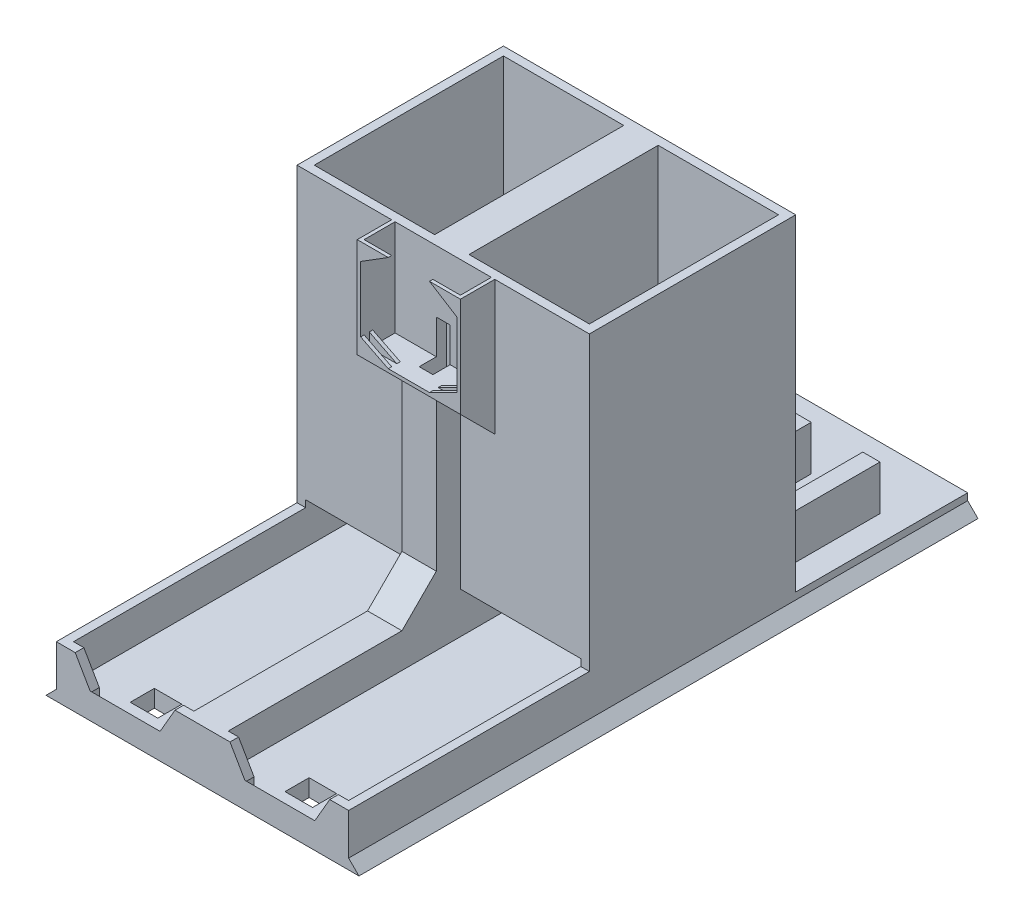
SolidWorks part; units mm, degrees
ref_plane "Front Plane" through (0, 0, 0) normal (0, 0, 1) x (1, 0, 0)
ref_plane "Top Plane" through (0, 0, 0) normal (0, 1, 0) x (1, 0, 0)
ref_plane "Right Plane" through (0, 0, 0) normal (1, 0, 0) x (0, 0, -1)
sketch "Sketch1" plane through (0, 0, 0) normal (0, 1, 0) x (1, 0, 0)
  line L1 (0, 0) -> (85, 0)
  line L2 (0, 0) -> (0, 60)
  line L3 (0, 60) -> (85, 60)
  line L4 (85, 0) -> (85, 60)
  dimension "D1" = 85
  dimension "D2" = 60
sketch "Sketch2" plane through (0, 0, 0) normal (0, 1, 0) x (1, 0, 0)
  line L1 (2.5, 57.5) -> (37.5, 57.5)
  line L2 (2.5, 57.5) -> (2.5, 2.5)
  line L3 (2.5, 2.5) -> (37.5, 2.5)
  line L4 (37.5, 57.5) -> (37.5, 2.5)
  line L5 (47.5, 57.5) -> (82.5, 57.5)
  line L6 (47.5, 57.5) -> (47.5, 2.5)
  line L7 (47.5, 2.5) -> (82.5, 2.5)
  line L8 (82.5, 57.5) -> (82.5, 2.5)
  dimension "D1" = 35
  dimension "D2" = 10
extrude "Boss-Extrude1" add sketch "Sketch1" along normal blind 100
extrude "Cut-Extrude1" cut sketch "Sketch2" along normal blind 95 from offset 5
sketch "Sketch3" plane through (0, 0, 0) normal (0, 0, 1) x (1, 0, 0)
  line L0 (85, 100) -> (85, 0) construction
  line L1 (0, 0) -> (85, 0)
  line L2 (0, 0) -> (0, 5)
  line L3 (0, 5) -> (85, 5)
  line L4 (85, 0) -> (85, 5)
extrude "Boss-Extrude2" add sketch "Sketch3" along normal blind 70
sketch "Sketch4" plane through (0, 5, 0) normal (0, 1, 0) x (1, 0, 0)
  line L0 (85, 0) -> (82.5, 0)
  line L5 (0, 0) -> (0, -70)
  line L18 (0, -70) -> (85, -70)
  line L19 (85, -70) -> (85, 0)
  line L20 (85, 0) -> (0, 0) construction
  line L21 (82.5, 0) -> (82.5, -67.5)
  line L22 (82.5, -67.5) -> (47.5, -67.5)
  line L23 (47.5, -67.5) -> (47.5, 0)
  line L24 (0, 0) -> (85, 0) construction
  line L25 (47.5, 0) -> (37.5, 0)
  line L26 (37.5, 0) -> (37.5, -67.5)
  line L27 (37.5, -67.5) -> (2.5, -67.5)
  line L28 (2.5, -67.5) -> (2.5, 0)
  line L29 (2.5, 0) -> (0, 0)
  dimension "D1" = 2.5
  dimension "D2" = 2.5
  dimension "D3" = 10
extrude "Boss-Extrude3" add sketch "Sketch4" along normal blind 10
sketch "Sketch5" plane through (0, 15, 0) normal (0, 1, 0) x (1, 0, 0)
  line L0 (37.5, -67.5) -> (2.5, -67.5) construction
  line L1 (10, -67.5) -> (30, -67.5)
  line L2 (10, -67.5) -> (10, -70)
  line L3 (10, -70) -> (30, -70)
  line L4 (30, -67.5) -> (30, -70)
  line L5 (0, -70) -> (85, -70) construction
  line L6 (82.5, -67.5) -> (47.5, -67.5) construction
  line L7 (75, -67.5) -> (55, -67.5)
  line L8 (75, -67.5) -> (75, -70)
  line L9 (75, -70) -> (55, -70)
  line L10 (55, -67.5) -> (55, -70)
  line L12 (37.5, 0) -> (37.5, -67.5) construction
  line L13 (47.5, -67.5) -> (47.5, 0) construction
  line L14 (82.5, 0) -> (82.5, -67.5) construction
  line L15 (2.5, -67.5) -> (2.5, 0) construction
  dimension "D1" = 7.5
  dimension "D2" = 7.5
  dimension "D3" = 7.5
  dimension "D4" = 7.5
extrude "Cut-Extrude2" cut sketch "Sketch5" against normal blind 7.5
sketch "Sketch6" plane through (0, 0, 0) normal (0, 0, 1) x (1, 0, 0)
  line L1 (2.5, 17) -> (37.5, 17)
  line L2 (2.5, 17) -> (2.5, 5)
  line L3 (2.5, 5) -> (37.5, 5)
  line L4 (37.5, 17) -> (37.5, 5)
  line L5 (47.5, 5) -> (82.5, 5)
  line L6 (47.5, 5) -> (47.5, 17)
  line L7 (47.5, 17) -> (82.5, 17)
  line L8 (82.5, 5) -> (82.5, 17)
  line L10 (0, 15) -> (0, 0) construction
  line L11 (85, 0) -> (85, 15) construction
  dimension "D1" = 2.5
  dimension "D2" = 10
  dimension "D3" = 2.5
extrude "Cut-Extrude4" cut sketch "Sketch6" against normal blind 57.5
sketch "Sketch7" plane through (0, 0, -60) normal (0, 0, -1) x (-1, 0, 0)
  line L0 (0, 15) -> (0, 0) construction
  line L1 (-85, 0) -> (-85, 15) construction
  circle A0 centre (-20, 11.5) radius 4
  circle A1 centre (-65, 11.5) radius 4
  dimension "D1" = 20
  dimension "D2" = 20
extrude "Cut-Extrude6" cut sketch "Sketch7" against normal up to next
sketch "Sketch9" plane through (0, 0, 0) normal (0, 1, 0) x (1, 0, 0)
  line L0 (85, 0) -> (85, 60) construction
  line L1 (0, 60) -> (85, 60)
  line L2 (0, 60) -> (0, 110)
  line L3 (0, 110) -> (85, 110)
  line L4 (85, 60) -> (85, 110)
  line L5 (0, 60) -> (0, 0) construction
extrude "Boss-Extrude4" add sketch "Sketch9" along normal blind 5
sketch "Sketch13" plane through (0, 5, 0) normal (0, 1, 0) x (1, 0, 0)
  line L1 (16, -64.5) -> (24, -64.5)
  line L2 (16, -64.5) -> (16, -57.5)
  line L3 (16, -57.5) -> (24, -57.5)
  line L4 (24, -64.5) -> (24, -57.5)
  line L5 (30, -67.5) -> (10, -67.5) construction
  line L10 (2.5, 57.5) -> (2.5, -67.5) construction
  line L11 (37.5, -67.5) -> (37.5, 57.5) construction
  line L12 (42.5, -70) -> (42.5, -52.9537) construction
  line L13 (30, -70) -> (55, -70) construction
  line L15 (61, -64.5) -> (61, -57.5)
  line L16 (69, -57.5) -> (61, -57.5)
  line L17 (69, -64.5) -> (69, -57.5)
  line L18 (69, -64.5) -> (61, -64.5)
  point P12 (16, -61)
  dimension "D1" = 13.5
  dimension "D2" = 13.5
  dimension "D3" = 7
  dimension "D4" = 3
extrude "Cut-Extrude8 (Button Holes)" cut sketch "Sketch13" against normal through all
sketch "Sketch14" plane through (0, 0, 0) normal (0, 0, 1) x (1, 0, 0)
  line L0 (0, 100) -> (85, 100) construction
  line L1 (27.5, 100) -> (28.5, 100)
  line L2 (27.5, 100) -> (27.5, 71)
  line L3 (27.5, 71) -> (32.8273, 71)
  line L4 (28.5, 100) -> (28.5, 72)
  line L6 (56.5, 100) -> (57.5, 100)
  line L7 (56.5, 100) -> (56.5, 72)
  line L8 (52.1727, 71) -> (57.5, 71)
  line L9 (57.5, 100) -> (57.5, 71)
  line L10 (32.8273, 71) -> (52.1727, 71)
  line L12 (28.5, 72) -> (56.5, 72)
  line L13 (85, 100) -> (85, 15) construction
  dimension "D1" = 29
  dimension "D2" = 1
  dimension "D3" = 1
  dimension "D4" = 28
  dimension "D5" = 1
  dimension "D6" = 27.5
extrude "Boss-Extrude5 (OLED Mount)" add sketch "Sketch14" along normal blind 10
sketch "Sketch15" plane through (0, 0, 10) normal (0, 0, 1) x (1, 0, 0)
  line L6 (42.5, 71) -> (42.5, 81.9127) construction
  line L7 (27.5, 71) -> (57.5, 71) construction
  line L8 (28.5, 72) -> (28.5, 100) construction
  line L14 (28.5, 72) -> (36.5, 72)
  line L15 (56.5, 72) -> (28.5, 72) construction
  line L16 (36.5, 72) -> (28.5, 76)
  line L17 (28.5, 76) -> (28.5, 72)
  line L18 (56.5, 76) -> (56.5, 72)
  line L19 (48.5, 72) -> (56.5, 76)
  line L20 (56.5, 72) -> (48.5, 72)
  dimension "D1" = 8
  dimension "D2" = 4
  dimension "D3" = 14
sketch "Sketch17" plane through (0, 0, 10) normal (0, 0, 1) x (1, 0, 0)
  line L0 (42.5, 100) -> (42.5, 89.7245) construction
  line L9 (28.5, 100) -> (56.5, 100) construction
  line L10 (56.5, 95) -> (56.5, 100)
  line L11 (48.5, 100) -> (56.5, 95)
  line L12 (28.5, 100) -> (36.5, 100)
  line L13 (36.5, 100) -> (28.5, 95)
  line L14 (28.5, 72) -> (28.5, 100) construction
  line L15 (28.5, 95) -> (28.5, 100)
  line L16 (56.5, 100) -> (48.5, 100)
  dimension "D1" = 8
  dimension "D2" = 5
extrude "Boss-Extrude6 (OLED Mount)" add sketch "Sketch15" against normal blind 1
extrude "Boss-Extrude7 (OLED Mount)" add sketch "Sketch15<2>" against normal blind 1 from offset 2.5 offset against normal yes
sketch "Sketch15<2>" plane through (0, 0, 10) normal (0, 0, 1) x (1, 0, 0) same geometry as "Sketch15"
extrude "Boss-Extrude8 (OLED Mount)" add sketch "Sketch17" against normal blind 1
sketch "Sketch32" plane through (27.5, 0, 0) normal (-1, 0, 0) x (0, 0, 1)
  line L0 (0, 71) -> (10, 71)
  line L1 (10, 71) -> (0, 61)
  line L3 (0, 61) -> (0, 71)
  line L4 (0, 15) -> (0, 17) construction
  dimension "D1" = 10
extrude "Boss-Extrude13 OLED Mount Support)" add sketch "Sketch32" against normal blind 30
sketch "Sketch18" plane through (0, 72, 0) normal (0, 1, 0) x (1, 0, 0)
  line L0 (28.5, 0) -> (56.5, 0) construction
  line L5 (47.5, 57.5) -> (47.5, -67.5) construction
  line L8 (40.5, 3) -> (44.5, 3)
  line L9 (40.5, 3) -> (40.5, -5)
  line L10 (40.5, -5) -> (44.5, -5)
  line L11 (44.5, 3) -> (44.5, -5)
  line L12 (37.5, -67.5) -> (37.5, 57.5) construction
  dimension "D1" = 3
  dimension "D2" = 3
  dimension "D3" = 3
  dimension "D4" = 5
extrude "Cut-Extrude9 (OLED Cable)" cut sketch "Sketch18" against normal through all and the other way blind 10
sketch "Sketch31" plane through (0, 15, 0) normal (0, 1, 0) x (1, 0, 0)
  line L0 (37.5, 0) -> (40.5, 0)
  line L1 (40.5, 0) -> (40.5, -5)
  line L2 (40.5, -5) -> (44.5, -5)
  line L3 (44.5, -5) -> (44.5, 0)
  line L4 (44.5, 0) -> (47.5, 0)
  line L5 (47.5, 0) -> (47.5, -7)
  line L6 (47.5, -7) -> (37.5, -7)
  line L7 (37.5, 0) -> (37.5, -67.5) construction
  line L8 (37.5, -7) -> (37.5, 0)
  dimension "D1" = 2
extrude "Boss-Extrude12 (OLED Cable Guide)" add sketch "Sketch31" along normal up to next
sketch "Sketch20" plane through (0, 5, 0) normal (0, 1, 0) x (1, 0, 0)
  line L0 (0, 60) -> (85, 60) construction
  line L1 (70, 60) -> (60, 60)
  line L2 (70, 60) -> (70, 70)
  line L3 (70, 70) -> (60, 70)
  line L4 (60, 60) -> (60, 70)
  line L5 (85, 60) -> (85, 110) construction
  line L7 (42.5, 110) -> (42.5, 60) construction
  line L8 (85, 110) -> (0, 110) construction
  line L9 (15, 70) -> (25, 70)
  line L10 (25, 60) -> (25, 70)
  line L11 (15, 60) -> (25, 60)
  line L12 (15, 60) -> (15, 70)
  point P8 (65, 60)
  dimension "D1" = 10
  dimension "D2" = 15
  dimension "D3" = 10
  dimension "D4" = 42.5
extrude "Cut-Extrude10 (Solenoid Wire Hole)" cut sketch "Sketch20" against normal through all
sketch "Sketch21" plane through (0, 5, 0) normal (0, 1, 0) x (1, 0, 0)
  line L0 (70, 60) -> (85, 60) construction
  line L1 (72.5, 60) -> (77.5, 60)
  line L2 (72.5, 60) -> (72.5, 92)
  line L3 (72.5, 92) -> (77.5, 92)
  line L4 (77.5, 60) -> (77.5, 92)
  line L7 (85, 110) -> (0, 110) construction
  line L9 (42.5, 60) -> (42.5, 110) construction
  line L10 (25, 60) -> (60, 60) construction
  line L11 (0, 110) -> (0, 60) construction
  line L12 (65, 110) -> (65, 60) construction
  line L13 (85, 60) -> (85, 110) construction
  line L15 (52.5, 60) -> (52.5, 92)
  line L16 (57.5, 92) -> (52.5, 92)
  line L17 (57.5, 60) -> (57.5, 92)
  line L18 (57.5, 60) -> (52.5, 60)
  line L19 (27.5, 60) -> (32.5, 60)
  line L20 (27.5, 60) -> (27.5, 92)
  line L21 (32.5, 60) -> (32.5, 92)
  line L22 (27.5, 92) -> (32.5, 92)
  line L23 (7.5, 60) -> (7.5, 92)
  line L24 (12.5, 92) -> (7.5, 92)
  line L25 (12.5, 60) -> (12.5, 92)
  line L26 (12.5, 60) -> (7.5, 60)
  dimension "D1" = 5
  dimension "D2" = 42.5
  dimension "D3" = 20
  dimension "D4" = 7.5
  dimension "D5" = 32
extrude "Boss-Extrude9 (Solenoid Side Support)" add sketch "Sketch21" along normal blind 13
chamfer "Chamfer3 (Thumb)" distance 2.5 angle 45 2 edges at (20, 7.5, 67.5) (65, 7.5, 67.5)
chamfer "Chamfer5 (Thumb)" distance 4.5 angle 60 4 edges at (75, 15, 68.75) (55, 15, 68.75) (30, 15, 68.75) (10, 15, 68.75) first distance on face at (80.8333, 15, 45.8333) first distance on face at (42.5, 15, 53) first distance on face at (4.1667, 15, 45.8333)
sketch "Sketch37" plane through (0, 0, 70) normal (0, 0, 1) x (1, 0, 0)
  line L0 (85, 0) -> (88, 0)
  line L1 (88, 0) -> (85, 3)
  line L2 (85, 0) -> (85, 15) construction
  line L3 (85, 3) -> (85, 0)
  line L4 (0, 0) -> (-3, 0)
  line L5 (-3, 0) -> (0, 3)
  line L6 (0, 15) -> (0, 0) construction
  line L7 (0, 3) -> (0, 0)
  dimension "D1" = 3
  dimension "D2" = 3
  dimension "D3" = 3
  dimension "D4" = 3
extrude "Boss-Extrude5 (Guide)" add sketch "Sketch37" against normal through all
sketch "Sketch49" plane through (0, 15, 0) normal (0, 1, 0) x (1, 0, 0)
  line L0 (47.5, -67.5) -> (47.5, -7) construction
  line L1 (37.5, -7) -> (47.5, -7)
  line L2 (37.5, -7) -> (37.5, -17)
  line L3 (37.5, -17) -> (47.5, -17)
  line L4 (47.5, -7) -> (47.5, -17)
  dimension "D1" = 10
extrude "Boss-Extrude14" add sketch "Sketch49" along normal blind 10
chamfer "Chamfer8" distance 10 angle 45 1 edges at (42.5, 25, 17)
